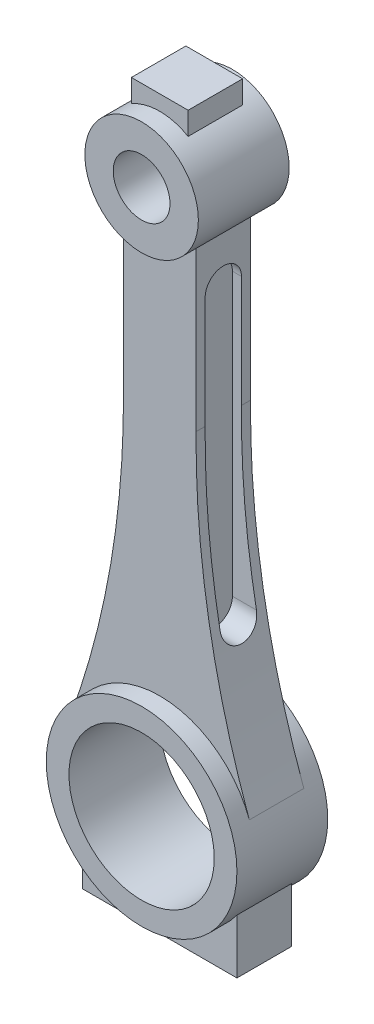
SolidWorks part; units mm, degrees
ref_plane "Front Plane" through (0, 0, 0) normal (0, 0, 1) x (1, 0, 0)
ref_plane "Top Plane" through (0, 0, 0) normal (0, 1, 0) x (1, 0, 0)
ref_plane "Right Plane" through (0, 0, 0) normal (1, 0, 0) x (0, 0, -1)
sketch "Sketch1" plane through (0, 0, 0) normal (0, 0, 1) x (1, 0, 0)
  line L0 (0, 4083.7787) -> (0, -1883.8789) construction
  line L1 (-203.2, 2804.041) -> (-203.2, 1915.041)
  line L2 (203.2, 2804.041) -> (203.2, 1915.041)
  line L3 (-158.75, 3322.9631) -> (-158.75, 3449.9631)
  line L4 (-158.75, 3449.9631) -> (158.75, 3449.9631)
  line L5 (158.75, 3449.9631) -> (158.75, 3322.9631)
  line L6 (-431.8, -313.1522) -> (-431.8, -617.9522)
  line L7 (-431.8, -617.9522) -> (431.8, -617.9522)
  line L8 (431.8, -617.9522) -> (431.8, -313.1522)
  circle A0 centre (0, 0) radius 533.4
  circle A1 centre (0, 0) radius 406.4
  circle A2 centre (0, 3048) radius 317.5
  circle A3 centre (0, 3048) radius 158.75
  arc A4 (-203.2, 1915.041) -> (-501.1129, 182.7605) centre (-5128.0444, 1870.2451) cw
  arc A5 (203.2, 1915.041) -> (501.1129, 182.7605) centre (5128.0444, 1870.2451) ccw
  dimension "D2" = 1066.8
  dimension "D3" = 812.8
  dimension "D4" = 635
  dimension "D5" = 317.5
  dimension "D1" = 3048
  dimension "D6" = 203.2
  dimension "D7" = 889
  dimension "D8" = 317.5
  dimension "D9" = 127
  dimension "D10" = 863.6
  dimension "D11" = 304.8
extrude "Boss-Extrude1" add sketch "Sketch1" along normal mid plane 508 contours A2 L0 A3 | L0 A2 A3 | A0 L0 A1 | L0 A0 A1 region at (80.3376, 3347.8238, 0) region at (-7.0995, 3286.125, 0) region at (298.9652, 427.2631, 0) region at (-11.9272, 469.9, 0)
extrude "Boss-Extrude2" add sketch "Sketch1<3>" along normal mid plane 304.8 contours A2 L0 A0 A5 L2 | L0 A2 L1 A4 A0 | L0 L4 L3 A2 | L4 L0 A2 L5 | A0 L0 L7 L8 | L0 A0 L6 L7 region at (85.0176, 3400.0426, 0) region at (-85.0176, 3400.0426, 0) region at (-135.7643, 1472.9259, 0) region at (135.7643, 1472.9259, 0) region at (-265.4141, -529.5837, 0) region at (265.4141, -529.5837, 0)
sketch "Sketch1<3>" plane through (0, 0, 0) normal (0, 0, 1) x (1, 0, 0) same geometry as "Sketch1"
sketch "Sketch2" plane through (0, 0, 0) normal (1, 0, 0) x (0, 0, -1)
  line L0 (0, 2540) -> (0, 965.2) construction
  line L1 (101.6, 2540) -> (101.6, 965.2)
  line L2 (-101.6, 2540) -> (-101.6, 965.2)
  line L3 (-254, 3048) -> (254, 3048) construction
  line L4 (-254, 3365.5) -> (-254, 2730.5) construction
  line L5 (254, 2730.5) -> (254, 3365.5) construction
  arc A0 (101.6, 2540) -> (-101.6, 2540) centre (0, 2540) ccw
  arc A1 (-101.6, 965.2) -> (101.6, 965.2) centre (0, 965.2) ccw
  point P2 (0, 1752.6)
  dimension "D2" = 101.6
  dimension "D1" = 1574.8
  dimension "D3" = 508
extrude "Cut-Extrude1" cut sketch "Sketch2" along normal through all from offset 152.4
extrude "Cut-Extrude2" cut sketch "Sketch2<2>" against normal through all from offset 152.4 offset against normal yes
sketch "Sketch2<2>" plane through (0, 0, 0) normal (1, 0, 0) x (0, 0, -1) same geometry as "Sketch2"
